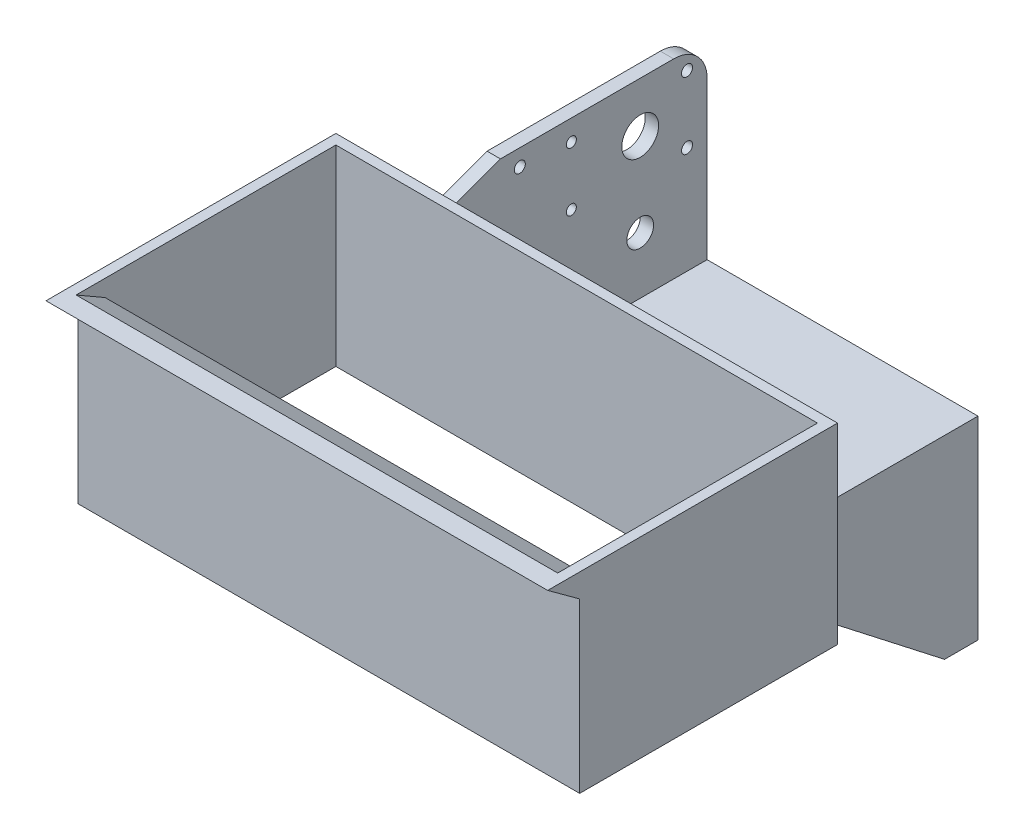
SolidWorks part; units mm, degrees
other "标注1"
sketch "草图12" plane through (40, 25, 80) normal (0.0849, 0.2202, 0.9717) x (0.9962, -0.0022, -0.0865)
ref_plane "前视基准面" through (0, 0, 0) normal (0, 0, 1) x (1, 0, 0)
ref_plane "上视基准面" through (0, 0, 0) normal (0, 1, 0) x (1, 0, 0)
ref_plane "右视基准面" through (0, 0, 0) normal (1, 0, 0) x (0, 0, -1)
sketch "草图1" plane through (0, 0, 0) normal (0, 0, 1) x (1, 0, 0)
  line L1 (-40, -25) -> (40, -25)
  line L2 (-40, -25) -> (-40, 25)
  line L3 (-40, 25) -> (40, 25)
  line L4 (40, -25) -> (40, 25)
  line L5 (-40, -25) -> (40, 25) construction
  line L6 (-40, 25) -> (40, -25) construction
  point P0 (0, 0)
  dimension "D1" = 80
  dimension "D2" = 50
extrude "凸台-拉伸1" add sketch "草图1" along normal blind 5
sketch "草图2" plane through (0, 0, 5) normal (0, 0, 1) x (1, 0, 0)
  line L0 (-1000, 0) -> (49000, 0) construction
  line L1 (0, -1000) -> (0, 49000) construction
  line L2 (-30, 20) -> (30, 20) construction
  line L3 (-30, 20) -> (-30, -20) construction
  line L4 (30, 20) -> (30, -20) construction
  line L5 (-30, -20) -> (30, -20) construction
  line L6 (0, 1000) -> (0, -49000) construction
  point P9 (0, 20)
  point P11 (30, 0)
  point P12 (-30, 0)
  point P14 (0, -20)
  dimension "D1" = 30
  dimension "D2" = 20
hole_wizard "M5 螺纹孔1" positions "草图3" profile "草图4" tap size "M5" standard "GB"
sketch "草图3" plane through (0, 0, 5) normal (0, 0, 1) x (1, 0, 0)
  point P0 (-30, 20)
  point P3 (-30, -20)
  point P6 (30, -20)
  point P9 (30, 20)
sketch "草图4" plane through (-30, 20, 5) normal (1, 0, 0) x (0, -1, 0)
  line L0 (0, 0) -> (0, 12.4)
  line L1 (0, 12.4) -> (2.1, 11.1382)
  line L2 (2.1, 11.1382) -> (2.1, 0)
  line L5 (2.1, 0) -> (0, 0)
  line L10 (0, 12.4) -> (-2.1, 11.1382) construction
  line L11 (0, -6.35) -> (0, 107.95) construction
  dimension "螺纹孔钻头直径" = 4.2
  dimension "螺纹孔钻头深度" = 12.4
  dimension "导头角度" = 118
cosmetic thread "孔螺蚊线1" parameters "D1"=10, "D2"=5
cosmetic thread "孔螺蚊线2" parameters "D1"=10, "D2"=5
cosmetic thread "孔螺蚊线3" parameters "D1"=10, "D2"=5
cosmetic thread "孔螺蚊线4" parameters "D1"=10, "D2"=5
sketch "草图5" plane through (40, 0, 0) normal (1, 0, 0) x (0, 0, -1)
  line L1 (0, -25) -> (-80, -25)
  line L2 (0, -25) -> (0, 25)
  line L3 (0, 25) -> (-80, 25)
  line L4 (-80, -25) -> (-80, 25)
  dimension "D1" = 50
  dimension "D2" = 80
extrude "凸台-拉伸2" add sketch "草图5" against normal blind 2 from offset 12 offset against normal yes
sketch "草图6" plane through (26, 0, 0) normal (-1, 0, 0) x (0, 0, 1)
  line L0 (11, 20) -> (61, 20) construction
  line L1 (61, 20) -> (61, 0) construction
  line L2 (61, 0) -> (11, 0) construction
  line L3 (11, 0) -> (11, 20) construction
  line L4 (5, 20) -> (5, -20) construction
  line L5 (5, 25) -> (80, 25) construction
  dimension "D1" = 50
  dimension "D2" = 20
  dimension "D3" = 6
  dimension "D4" = 5
hole_wizard "M4 螺纹孔1" positions "草图7" profile "草图8" tap size "M4" standard "GB"
sketch "草图7" plane through (26, 0, 0) normal (-1, 0, 0) x (0, 0, 1)
  point P0 (11, 20)
  point P3 (11, 0)
  point P6 (61, 20)
  point P9 (61, 0)
sketch "草图8" plane through (26, 20, 11) normal (0, 1, 0) x (0, 0, 1)
  line L0 (0, 0) -> (0, 10.1)
  line L1 (0, 10.1) -> (1.65, 9.1086)
  line L2 (1.65, 9.1086) -> (1.65, 0)
  line L5 (1.65, 0) -> (0, 0)
  line L10 (0, 10.1) -> (-1.65, 9.1086) construction
  line L11 (0, -6.35) -> (0, 107.95) construction
  dimension "螺纹孔钻头直径" = 3.3
  dimension "螺纹孔钻头深度" = 10.1
  dimension "导头角度" = 118
cosmetic thread "孔螺蚊线7" parameters "D1"=8, "D2"=4
cosmetic thread "孔螺蚊线8" parameters "D1"=8, "D2"=4
cosmetic thread "孔螺蚊线9" parameters "D1"=8, "D2"=4
cosmetic thread "孔螺蚊线10" parameters "D1"=8, "D2"=4
sketch "草图11" plane through (26, 0, 0) normal (-1, 0, 0) x (0, 0, 1)
  line L0 (25, 10) -> (62.4996, 10) construction
  line L2 (11, 0) -> (11, 20) construction
  line L5 (5, 25) -> (80, 25) construction
  line L9 (5, 25) -> (5, -25) construction
  circle A0 centre (25, 10) radius 5.5
  circle A1 centre (45.6, 18.75) radius 1.5
  circle A2 centre (45.6, 1.25) radius 1.5
  dimension "D1" = 11
  dimension "D2" = 3
  dimension "D3" = 17.5
  dimension "D4" = 20.6
  dimension "D5" = 15
  dimension "D6" = 20
extrude "切除-拉伸1" cut sketch "草图11" against normal through all
mirror "镜向1" about plane through (0, 0, 0) normal (1, 0, 0) of "凸台-拉伸2"
mirror "镜向2" about plane through (0, 0, 0) normal (1, 0, 0) of "M4 螺纹孔1", "切除-拉伸1"
cosmetic thread "孔螺蚊线11" parameters "D1"=8, "D2"=4
cosmetic thread "孔螺蚊线12" parameters "D1"=8, "D2"=4
cosmetic thread "孔螺蚊线13" parameters "D1"=8, "D2"=4
cosmetic thread "孔螺蚊线14" parameters "D1"=8, "D2"=4
sketch "草图13" plane through (0, -25, 0) normal (0, -1, 0) x (1, 0, 0)
  line L1 (-28, 80) -> (28, 80)
  line L2 (-28, 80) -> (-28, 5)
  line L3 (-28, 5) -> (28, 5)
  line L4 (28, 80) -> (28, 5)
  line L5 (-40, 5) -> (41.8748, 5)
  line L6 (-40, 5) -> (-40, -4.9337)
  line L7 (-40, -4.9337) -> (41.8748, -4.9337)
  line L8 (41.8748, 5) -> (41.8748, -4.9337)
  line M1 (-40, 0) -> (40, 0)
  line M2 (40, 0) -> (40, 5)
  line M3 (40, 5) -> (28, 5)
  line M4 (28, 5) -> (28, 80)
  line M5 (28, 80) -> (26, 80)
  line M6 (26, 80) -> (26, 5)
  line M7 (26, 5) -> (-26, 5)
  line M8 (-26, 5) -> (-26, 80)
  line M9 (-26, 80) -> (-28, 80)
  line M10 (-28, 80) -> (-28, 5)
  line M11 (-28, 5) -> (-40, 5)
  line M12 (-40, 5) -> (-40, 0)
extrude "切除-拉伸2" cut sketch "草图13" against normal through all both and the other way through all contours L3 M11 M12 M1 M2 M3 M7 | L8 L5 L6 L7 M2 M1 region at (0, -25, 2.5) region at (1.8445, -25, -2.3542)
sketch "草图14" plane through (0, 0, 5) normal (0, 0, -1) x (-1, 0, 0)
  line L1 (-28, 25) -> (28, 25)
  line L2 (-28, 25) -> (-28, -25)
  line L3 (-28, -25) -> (28, -25)
  line L4 (28, 25) -> (28, -25)
extrude "凸台-拉伸4" add sketch "草图13<3>" along normal blind 75 contours L1 M8 M7 M6 | L3 M10 M8 M9 | L3 M6 M4 M5 region at (-27, -25, 42.5) region at (0, -25, 42.5) region at (27, -25, 42.5)
sketch "草图13<3>" plane through (0, -25, 0) normal (0, -1, 0) x (1, 0, 0) same geometry as "草图13"
sketch "草图16" plane through (0, 0, 5) normal (0, 0, -1) x (-1, 0, 0)
  line L0 (0, -100) -> (0, -90.6573) construction
  line L2 (-28, -100) -> (28, -100) construction
  line L3 (-40, -100) -> (40, -100)
  line L4 (-40, -100) -> (-40, -46)
  line L5 (-40, -46) -> (40, -46)
  line L6 (40, -100) -> (40, -46)
  line L7 (12, -73) -> (0.1128, -73) construction
  circle A0 centre (-12, -83) radius 2.1
  circle A1 centre (12, -83) radius 2.1
  circle A2 centre (-12, -63) radius 2.1
  circle A3 centre (12, -63) radius 2.1
  point P15 (0, -46)
  dimension "D1" = 4.2
  dimension "D3" = 4.2
  dimension "D2" = 12
  dimension "D4" = 20
  dimension "D5" = 40
  dimension "D6" = 27
  dimension "D7" = 10
  dimension "D8" = 27
  dimension "D9" = 24
extrude "凸台-拉伸5" add sketch "草图16" against normal blind 10
sketch "草图17" plane through (0, 0, 80) normal (0, 0, 1) x (1, 0, 0)
  line L0 (-26, -49) -> (-26, -100)
  line L1 (26, -49) -> (26, -100)
  line L2 (-26, -49) -> (26, -49)
  line L3 (0, -100) -> (0, -92.4239) construction
  line L8 (28, -100) -> (28, 25)
  line L9 (28, 25) -> (26, 25)
  line L10 (26, 25) -> (26, -25)
  line L11 (26, -25) -> (-26, -25)
  line L12 (-26, -25) -> (-26, 25)
  line L13 (-26, 25) -> (-28, 25)
  line L14 (-28, 25) -> (-28, -100)
  line L15 (-28, -100) -> (28, -100)
  line L23 (-26, -100) -> (26, -100)
  dimension "D2" = 51
  dimension "D3" = 52
  dimension "D4" = 26
  dimension "D1" = 0
extrude "切除-拉伸4" cut sketch "草图17" against normal up to surface (65 mm away) up to face at (34, -73, 15)
sketch "草图18" plane through (0, 0, 80) normal (0, 0, 1) x (1, 0, 0)
  line L0 (0, -10.6953) -> (0, -25) construction
  line L1 (-50, 25) -> (50, 25)
  line L2 (-50, 25) -> (-50, -25)
  line L3 (-50, -25) -> (50, -25)
  line L4 (50, 25) -> (50, -25)
  line L5 (-26, -49) -> (26, -49) construction
  line L6 (-48, 25) -> (-48, -20)
  line L7 (48, 25) -> (48, -20)
  line L9 (-48, -20) -> (48, -20)
  point P5 (0, 25)
  line M11 (28, -100) -> (28, 25)
  line M13 (26, 25) -> (26, -25)
  line M14 (26, -25) -> (-26, -25)
  line M15 (-26, -25) -> (-26, 25)
  line M17 (-28, 25) -> (-28, -100)
  dimension "D1" = 50
  dimension "D2" = 50
  dimension "D3" = 74
  dimension "D4" = 2
  dimension "D5" = 2
  dimension "D6" = 5
extrude "凸台-拉伸6" add sketch "草图18" against normal up to surface (75 mm away) contours L9 L6 L1 L2 L3 M17 | L0 L9 L3 M15 | L9 L3 M17 M15 | L9 L0 M14 M13 | L9 L3 M13 M11 | L9 L3 L4 L1 L7 M11 region at (13, -22.5, 80) region at (-13, -22.5, 80) region at (-27, -22.5, 80) region at (27, -22.5, 80) region at (-28.5463, -22.5, 80) region at (38, -20.5463, 80)
sketch "草图19" plane through (-50, 0, 0) normal (-1, 0, 0) x (0, 0, 1)
  line L4 (80, 25) -> (5, 25)
  line L5 (5, 25) -> (5, -25)
  line L6 (5, -25) -> (80, -25)
  line L7 (80, -25) -> (80, 25)
  line L8 (80, 25) -> (5, 25)
  line L9 (5, 25) -> (5, -25)
  line L10 (5, -25) -> (80, -25)
  line L11 (80, -25) -> (80, 25)
  circle A0 centre (45.6, 1.25) radius 1.5 construction
  circle A1 centre (45.6, 18.75) radius 1.5 construction
  circle A2 centre (25, 10) radius 5.5 construction
  circle A3 centre (45.6, 1.25) radius 1.5
  circle A4 centre (45.6, 18.75) radius 1.5
  circle A5 centre (25, 10) radius 5.5
  dimension "D1" = 0
extrude "切除-拉伸5" cut sketch "草图19" against normal through all both and the other way through all contours A5 | A4 | A3 region at (-50, 1.25, 45.6) region at (-50, 18.75, 45.6) region at (-50, 10, 25)
sketch "草图20" plane through (-50, 0, 0) normal (-1, 0, 0) x (0, 0, 1)
  line L0 (61, 20) -> (61, 0) construction
  line L1 (61, 0) -> (11, 0) construction
  line L2 (11, 0) -> (11, 20) construction
  line L3 (11, 20) -> (61, 20) construction
  line L4 (61, 20) -> (61, 0) construction
  line L5 (61, 0) -> (11, 0) construction
  line L6 (11, 0) -> (11, 20) construction
  line L7 (11, 20) -> (61, 20) construction
ref_plane "基准面1" through (-50, 0, 0) normal (-1, 0, 0) x (0, 0, 1)
ref_plane "基准面2" through (-11, 0, 0) normal (-1, 0, 0) x (0, 0, 1)
mirror "镜向3" about plane through (-11, 0, 0) normal (-1, 0, 0) of "M4 螺纹孔1"
cosmetic thread "孔螺蚊线15" parameters "D1"=8, "D2"=4
cosmetic thread "孔螺蚊线16" parameters "D1"=8, "D2"=4
cosmetic thread "孔螺蚊线17" parameters "D1"=8, "D2"=4
cosmetic thread "孔螺蚊线18" parameters "D1"=8, "D2"=4
ref_plane "基准面3" through (50, 0, 0) normal (1, 0, 0) x (0, 0, -1)
ref_plane "基准面4" through (38, 0, 0) normal (1, 0, 0) x (0, 0, -1)
mirror "镜向4" about plane through (38, 0, 0) normal (1, 0, 0) of "M4 螺纹孔1"
cosmetic thread "孔螺蚊线19" parameters "D1"=8, "D2"=4
cosmetic thread "孔螺蚊线20" parameters "D1"=8, "D2"=4
cosmetic thread "孔螺蚊线21" parameters "D1"=8, "D2"=4
cosmetic thread "孔螺蚊线22" parameters "D1"=8, "D2"=4
sketch "草图21" plane through (0, 0, 80) normal (0, 0, 1) x (1, 0, 0)
  line L0 (-31.7586, 26.7655) -> (-31.7586, -20)
  line L1 (-48, -20) -> (-28, -20) construction
  line L2 (-31.7586, -20) -> (32.4376, -20)
  line L3 (28, -20) -> (48, -20) construction
  line L4 (32.4376, -20) -> (32.4376, 28.4059)
  line L5 (32.4376, 28.4059) -> (-31.7586, 26.7655)
extrude "切除-拉伸6" cut sketch "草图21" against normal through all both and the other way through all
sketch "草图22" plane through (0, 0, 80) normal (0, 0, 1) x (1, 0, 0)
  line L0 (-50, -25) -> (-28, -25) construction
  line L1 (-55, 25) -> (55, 25)
  line L2 (-55, 25) -> (-55, -25)
  line L3 (-55, -25) -> (55, -25)
  line L4 (55, 25) -> (55, -25)
  line L5 (-50, 25) -> (-48, 25) construction
  line L6 (0, -20) -> (0, 1.8911) construction
  line L8 (-53, 25) -> (-53, -20)
  line L9 (53, 25) -> (53, -20)
  line L10 (-53, -20) -> (53, -20)
  point P9 (0, 25)
  line M9 (48, -20) -> (-48, -20)
  line M12 (-50, 25) -> (-50, -25)
  line M13 (-50, -25) -> (-28, -25)
  line M21 (28, -25) -> (50, -25)
  line M22 (50, -25) -> (50, 25)
  dimension "D1" = 55
  dimension "D2" = 2
  dimension "D3" = 2
extrude "凸台-拉伸7" add sketch "草图22" against normal up to surface (75 mm away) contours L3 L6 L10 M12 M13 | L10 L8 L1 L2 L3 M12 | L6 L3 L10 M21 M22 M9 | L10 L3 L4 L1 L9 M22 region at (-53.6739, -2.9348, 80) region at (0, -22.5, 80) region at (53.6739, -2.9348, 80)
ref_plane "基准面6" through (-51.5, 0, 0) normal (1, 0, 0) x (0, 0, -1)
mirror "镜向8" about plane through (-51.5, 0, 0) normal (1, 0, 0) of "切除-拉伸5"
sketch "草图23" plane through (-55, 0, 0) normal (-1, 0, 0) x (0, 0, 1)
  line L0 (61, 20) -> (61, 0) construction
  line L1 (11, 20) -> (61, 20) construction
  line L2 (11, 0) -> (11, 20) construction
  line L3 (61, 0) -> (11, 0) construction
  line L4 (61, 20) -> (61, 0) construction
  line L5 (11, 20) -> (61, 20) construction
  line L6 (11, 0) -> (11, 20) construction
  line L7 (61, 0) -> (11, 0) construction
ref_plane "基准面7" through (2.5, 0, 0) normal (-1, 0, 0) x (0, 0, 1)
mirror "镜向16" about plane through (2.5, 0, 0) normal (-1, 0, 0) of "镜向3"
cosmetic thread "孔螺蚊线23" parameters "D1"=8, "D2"=4
cosmetic thread "孔螺蚊线24" parameters "D1"=8, "D2"=4
cosmetic thread "孔螺蚊线25" parameters "D1"=8, "D2"=4
cosmetic thread "孔螺蚊线26" parameters "D1"=8, "D2"=4
mirror "镜向18" about plane through (0, 0, 0) normal (1, 0, 0) of "镜向16"
cosmetic thread "孔螺蚊线27" parameters "D1"=8, "D2"=4
cosmetic thread "孔螺蚊线28" parameters "D1"=8, "D2"=4
cosmetic thread "孔螺蚊线29" parameters "D1"=8, "D2"=4
cosmetic thread "孔螺蚊线30" parameters "D1"=8, "D2"=4
sketch "草图24" plane through (0, 0, 5) normal (0, 0, -1) x (-1, 0, 0)
  line L0 (50, -20) -> (53, -20) construction
  line L1 (-51.4758, 28.456) -> (51.5, 28.456)
  line L2 (-51.4758, 28.456) -> (-51.4758, -20)
  line L3 (-51.4758, -20) -> (51.5, -20)
  line L4 (51.5, 28.456) -> (51.5, -20)
extrude "切除-拉伸7" cut sketch "草图24" against normal through all both and the other way through all
sketch "草图25" plane through (0, 0, 5) normal (0, 0, -1) x (-1, 0, 0)
  line L0 (0, -20) -> (0, -32.9926) construction
  line L6 (-55, 25) -> (-55, -25) construction
  line L7 (-53, -25) -> (-53, -32)
  line L8 (-53, -32) -> (53, -32)
  line L9 (-55, -25) -> (-55, -37)
  line L10 (-55, -37) -> (55, -37)
  line L11 (53, -25) -> (53, -32)
  line L12 (55, -25) -> (55, -37)
  line L13 (55, -25) -> (28, -25) construction
  line L14 (-55, -25) -> (-53, -25)
  line L15 (53, -25) -> (55, -25)
  point P13 (0, -37)
  point P16 (0, -32)
  dimension "D1" = 5
  dimension "D2" = 12
  dimension "D3" = 2
extrude "凸台-拉伸8" add sketch "草图25" against normal up to surface (75 mm away) up to face at (0, -33.625, 80)
sketch "草图26" plane through (0, 0, 5) normal (0, 0, -1) x (-1, 0, 0)
  line L0 (-53, -20) -> (-53, -32)
  line L1 (-53, -32) -> (53, -32)
  line L2 (53, -32) -> (53, -15.707)
  line L3 (53, 25) -> (53, -20) construction
  line L4 (53, -15.707) -> (-53, -15.707)
  line L5 (-53, 25) -> (-53, -20) construction
  line L6 (-53, -15.707) -> (-53, -20)
extrude "切除-拉伸8" cut sketch "草图26" against normal through all both and the other way through all
sketch "草图27" plane through (0, 0, 5) normal (0, 0, -1) x (-1, 0, 0)
  line L0 (0, -32) -> (0, -12.5887) construction
  line L2 (-59, 25) -> (-59, -37)
  line L3 (-59, -37) -> (59, -37)
  line L4 (59, 25) -> (59, -37)
  line L5 (55, 25) -> (55, -37) construction
  line L6 (-55, 25) -> (-55, -37) construction
  line L7 (-55, -37) -> (-28, -37) construction
  line L8 (59, 25) -> (57, 25)
  line L9 (57, 25) -> (57, -32)
  line L10 (57, -32) -> (-57, -32)
  line L11 (-57, -32) -> (-57, 25)
  line L12 (-57, 25) -> (-59, 25)
  line L13 (53, -32) -> (-53, -32) construction
  dimension "D1" = 4
  dimension "D2" = 4
  dimension "D3" = 2
  dimension "D4" = 2
  dimension "D5" = 62
extrude "凸台-拉伸9" add sketch "草图27" against normal up to surface (75 mm away) up to face at (0, -38.125, 80)
ref_plane "基准面8" through (56, 0, 0) normal (1, 0, 0) x (0, 0, -1)
mirror "镜向20" about plane through (56, 0, 0) normal (1, 0, 0) of "镜向8", "镜向16"
cosmetic thread "孔螺蚊线31" parameters "D1"=8, "D2"=4
cosmetic thread "孔螺蚊线32" parameters "D1"=8, "D2"=4
cosmetic thread "孔螺蚊线33" parameters "D1"=8, "D2"=4
cosmetic thread "孔螺蚊线34" parameters "D1"=8, "D2"=4
mirror "镜向22" about plane through (0, 0, 0) normal (1, 0, 0) of "镜向20"
cosmetic thread "孔螺蚊线35" parameters "D1"=8, "D2"=4
cosmetic thread "孔螺蚊线36" parameters "D1"=8, "D2"=4
cosmetic thread "孔螺蚊线37" parameters "D1"=8, "D2"=4
cosmetic thread "孔螺蚊线38" parameters "D1"=8, "D2"=4
sketch "草图28" plane through (0, 0, 5) normal (0, 0, -1) x (-1, 0, 0)
  line L0 (-56, 55) -> (-56, -55) construction
  line L1 (-56, 27.6586) -> (56, 27.6586)
  line L2 (-56, 27.6586) -> (-56, -32)
  line L3 (-56, -32) -> (56, -32)
  line L4 (56, 27.6586) -> (56, -32)
  line L5 (57, -32) -> (55, -32) construction
extrude "切除-拉伸9" cut sketch "草图28" against normal blind 100
sketch "草图29" plane through (0, 0, 80) normal (0, 0, 1) x (1, 0, 0)
  line L0 (0, -32) -> (0, -19.2163) construction
  line L2 (-75, 25) -> (75, 25)
  line L3 (28, 25) -> (-28, 25) construction
  line L4 (-75, 25) -> (-75, -37.1567)
  line L5 (-75, -37.1567) -> (75, -37.1567)
  line L6 (75, 25) -> (75, -37.1567)
  point P12 (0, 25)
  point P13 (0, -37.1567)
  dimension "D1" = 75
  dimension "D2" = 62.1567
extrude "凸台-拉伸10" add sketch "草图29" along normal blind 95
sketch "草图30" plane through (-75, 0, 0) normal (-1, 0, 0) x (0, 0, 1)
  line L0 (175, 25) -> (145, 7.6795)
  line L1 (145, 7.6795) -> (145, -37.1567)
  line L2 (175, -37.1567) -> (80, -37.1567) construction
  line L3 (175, 25) -> (175, -37.1567) construction
  dimension "D1" = 30
  dimension "D2" = 60
extrude "切除-拉伸10" cut sketch "草图30" against normal through all and the other way through all
sketch "草图31" plane through (-75, 0, 0) normal (-1, 0, 0) x (0, 0, 1)
  line L0 (83, 29.8275) -> (177.3615, 29.8275)
  line L1 (177.3615, 29.8275) -> (142, 9.4115)
  line L2 (142, 9.4115) -> (142, -50.3087)
  line L3 (142, -50.3087) -> (83, -50.3087)
  line L4 (83, -50.3087) -> (83, 29.8275)
  line L6 (80, 25) -> (80, -37.1567) construction
  line L7 (175, 25) -> (145, 7.6795) construction
  line L8 (145, 7.6795) -> (145, -37.1567) construction
  dimension "D2" = 3
  dimension "D3" = 3
  dimension "D4" = 3
extrude "切除-拉伸11" cut sketch "草图31" against normal offset from surface (144 mm away) 3 from offset 3 up to face at (75, -3.3268, 125) offset against normal yes
sketch "草图32" plane through (28, 0, 0) normal (1, 0, 0) x (0, 0, -1)
  line L0 (-80, -37.1567) -> (-15, -100)
  line L1 (-15, -100) -> (-94.5487, -113.2548)
  line L2 (-94.5487, -113.2548) -> (-80, -37.1567)
extrude "切除-拉伸12" cut sketch "草图32" along normal through all both and the other way through all
sketch "草图34" plane through (59, 0, 0) normal (1, 0, 0) x (0, 0, -1)
  line L0 (-80, 25) -> (-80, -37) construction
  line L1 (-5, 25) -> (-5, -25) construction
  line L3 (-14, -1.05) -> (-59, -1.05)
  line L4 (-80, 25) -> (-5, 25) construction
  line L5 (-59, -1.05) -> (-59, -4.05)
  line L6 (-59, -4.05) -> (-14, -4.05)
  line L7 (-14, -4.05) -> (-14, -1.05)
  dimension "D1" = 3
  dimension "D2" = 21
  dimension "D3" = 26.05
  dimension "D4" = 9
extrude "凸台-拉伸11" add sketch "草图34" along normal blind 20
extrude "凸台-拉伸12" add sketch "草图34<3>" against normal blind 20 from surface starting at face at (-59, 0, 59.35)
sketch "草图34<3>" plane through (59, 0, 0) normal (1, 0, 0) x (0, 0, -1) same geometry as "草图34"
sketch "草图35" plane through (0, 0, 5) normal (0, 0, -1) x (-1, 0, 0)
  line L0 (-28, -46) -> (-28, -100)
  line L5 (28, -46) -> (28, -100)
  line L10 (-40, -100) -> (40, -100)
  line L11 (40, -100) -> (40, -46)
  line L12 (40, -46) -> (-40, -46)
  line L13 (-40, -46) -> (-40, -100)
  line L14 (-40, -100) -> (40, -100)
  line L15 (40, -100) -> (40, -46)
  line L16 (40, -46) -> (-40, -46)
  line L17 (-40, -46) -> (-40, -100)
  circle A1 centre (12, -63) radius 2.1
  circle A2 centre (12, -63) radius 2.1
  circle A3 centre (-12, -63) radius 2.1
  circle A4 centre (-12, -63) radius 2.1
  circle A5 centre (12, -83) radius 2.1
  circle A6 centre (12, -83) radius 2.1
  circle A7 centre (-12, -83) radius 2.1
  circle A8 centre (-12, -83) radius 2.1
  point P0 (0, -71.1595)
  line M7 (-28, -46) -> (-40, -46)
  line M8 (-40, -46) -> (-40, -100)
  line M9 (-40, -100) -> (40, -100)
  line M10 (40, -100) -> (40, -46)
  line M11 (40, -46) -> (28, -46)
  dimension "D1" = 0
  dimension "D2" = 0
  dimension "D3" = 0
  dimension "D4" = 0
  dimension "D5" = 0
extrude "切除-拉伸13" cut sketch "草图35" against normal blind 10 contours A4 | A8 | A2 | A6 | L0 M7 M8 M9 | L5 M11 M9 M10 region at (34, -73, 5) region at (-34, -73, 5) region at (-12, -63, 5) region at (12, -63, 5) region at (-12, -83, 5) region at (12, -83, 5)
ref_plane "基准面9" through (-35, 0, 0) normal (1, 0, 0) x (0, 0, -1)
sketch "草图37" plane through (-35, 0, 0) normal (1, 0, 0) x (0, 0, -1)
  line L4 (-80, -37) -> (-5, -37)
  line L5 (-80, 25) -> (-80, -37)
  line L6 (-5, 25) -> (-80, 25)
  line L7 (-5, -37) -> (-5, 25)
  line L8 (-80, -37) -> (-5, -37)
  line L9 (-80, 25) -> (-80, -37)
  line L10 (-5, 25) -> (-80, 25)
  line L11 (-5, -37) -> (-5, 25)
  circle A0 centre (-11, 20) radius 1.65 construction
  circle A1 centre (-11, 0) radius 1.65 construction
  circle A2 centre (-45.6, 1.25) radius 1.5 construction
  circle A3 centre (-45.6, 18.75) radius 1.5 construction
  circle A4 centre (-25, 10) radius 5.5 construction
  circle A5 centre (-25, 10) radius 5.5
  circle A6 centre (-45.6, 18.75) radius 1.5
  circle A7 centre (-45.6, 1.25) radius 1.5
  circle A8 centre (-11, 0) radius 1.65
  circle A9 centre (-11, 20) radius 1.65
  circle A10 centre (-61, 20) radius 1.65 construction
  circle A11 centre (-61, 20) radius 1.65
  dimension "D1" = 0
extrude "凸台-拉伸13" add sketch "草图37" against normal blind 3
sketch "草图38" plane through (-38, 0, 0) normal (-1, 0, 0) x (0, 0, 1)
  line L4 (59, -1.05) -> (14, -1.05)
  line L5 (14, -1.05) -> (14, -4.05)
  line L6 (14, -4.05) -> (59, -4.05)
  line L7 (59, -4.05) -> (59, -1.05)
  line L8 (59, -1.05) -> (14, -1.05)
  line L9 (14, -1.05) -> (14, -4.05)
  line L10 (14, -4.05) -> (59, -4.05)
  line L11 (59, -4.05) -> (59, -1.05)
  dimension "D1" = 0
extrude "凸台-拉伸14" add sketch "草图38" along normal blind 20
sketch "草图39" plane through (0, 0, 80) normal (0, 0, -1) x (-1, 0, 0)
  line L0 (-42, -48.9981) -> (-42, 26.7782)
  line L2 (-42, 26.7782) -> (-75.2607, 26.7782)
  line L3 (-75.2607, 26.7782) -> (-96.9111, 26.7782)
  line L4 (-96.9111, 26.7782) -> (-96.9111, -48.9981)
  line L5 (-96.9111, -48.9981) -> (-42, -48.9981)
  line L6 (54.7, 26.7782) -> (54.7, -26.8557)
  line L7 (54.7, -26.8557) -> (38, -26.8557)
  line L8 (38, 25) -> (38, -32) construction
  line L9 (38, -26.8557) -> (38, -47.85)
  line L10 (38, -47.85) -> (95.8685, -47.85)
  line L11 (95.8685, -47.85) -> (95.8685, 12.0166)
  line L12 (95.8685, 12.0166) -> (66.1813, 27.9264)
  line L13 (66.1813, 27.9264) -> (54.7, 26.7782)
  line L15 (28, -100) -> (28, -37) construction
  dimension "D1" = 70
extrude "切除-拉伸17" cut sketch "草图39" along normal up to next contours L12 L13 L6 L7 L9 L10 L11 | L4 L5 L0 L2 L3 region at (-71.3932, -15.3982, 80)
sketch "草图40" plane through (-38, 0, 0) normal (-1, 0, 0) x (0, 0, 1)
  line L0 (5, -37) -> (5, 25) construction
  line L1 (5, 25) -> (80, 25) construction
  line L2 (42.5, 25) -> (42.5, -12.8603) construction
  circle A0 centre (25, -15) radius 4
  circle A1 centre (60, -15) radius 4
  dimension "D1" = 8
  dimension "D2" = 20
  dimension "D3" = 40
extrude "切除-拉伸18" cut sketch "草图40" against normal through all both and the other way through all
sketch "草图46" plane through (0, 0, 5) normal (0, 0, -1) x (-1, 0, 0)
  line L0 (12, -43.8944) -> (12, -95.6953) construction
  line L1 (28, -100) -> (28, -37) construction
  line L2 (-12, -83) -> (18.0205, -83) construction
  line L3 (-12, -63) -> (18.0205, -63) construction
  line L4 (-12, -63) -> (-43.3439, -63) construction
  line L5 (-12, -83) -> (-43.3439, -83) construction
  line L6 (4, -44.5419) -> (4, -84.5112) construction
  line L7 (-20, -41.7847) -> (-20, -84.5112) construction
  line L8 (-28, -43.8944) -> (-28, -90) construction
  line L10 (-28, -100) -> (28, -100) construction
  line L11 (-28, -90) -> (14.1348, -90) construction
  circle A0 centre (4, -63) radius 2.1
  circle A1 centre (-20, -63) radius 2.1
  circle A2 centre (-20, -83) radius 2.1
  circle A3 centre (4, -83) radius 2.1
  dimension "D3" = 4.2
  dimension "D5" = 4.2
  dimension "D7" = 4.2
  dimension "D8" = 4.2
  dimension "D1" = 16
  dimension "D2" = 8
  dimension "D4" = 24
  dimension "D6" = 8
  dimension "D9" = 10
sketch "草图48" plane through (0, 0, 5) normal (0, 0, -1) x (-1, 0, 0)
  line L1 (-15.9536, -56.9415) -> (-8.4612, -56.9415)
  line L2 (-15.9536, -56.9415) -> (-15.9536, -86.6527)
  line L3 (-15.9536, -86.6527) -> (-8.4612, -86.6527)
  line L4 (-8.4612, -56.9415) -> (-8.4612, -86.6527)
  line L5 (8.5904, -56.9415) -> (17.2454, -56.9415)
  line L6 (8.5904, -56.9415) -> (8.5904, -86.6527)
  line L7 (8.5904, -86.6527) -> (17.2454, -86.6527)
  line L8 (17.2454, -56.9415) -> (17.2454, -86.6527)
extrude "凸台-拉伸18" add sketch "草图48" against normal up to surface (10 mm away) up to face at (9.9, -83, 15)
sketch "草图49" plane through (0, 0, 5) normal (0, 0, -1) x (-1, 0, 0)
  line L0 (-28, -90) -> (12, -90)
  line L1 (12, -43.8944) -> (12, -95.6953) construction
  line L2 (-28, -90) -> (14.1348, -90) construction
  line L3 (12, -90) -> (12, -37.1567)
  line L4 (12, -37.1567) -> (28, -37)
  line L5 (28, -37) -> (28, -104.6086)
  line L6 (28, -104.6086) -> (-42.5646, -106.288)
  line L7 (-42.5646, -106.288) -> (-39.8518, -88.332)
  line L8 (-39.8518, -88.332) -> (-28, -90)
extrude "切除-拉伸20" cut sketch "草图49" against normal through all both and the other way through all
sketch "草图50" plane through (26, 0, 0) normal (-1, 0, 0) x (0, 0, 1)
  line L4 (15, -49) -> (15, -90)
  line L5 (15, -90) -> (25.3432, -90)
  line L6 (25.3432, -90) -> (67.7502, -49)
  line L7 (67.7502, -49) -> (15, -49)
  line L8 (15, -49) -> (15, -90)
  line L9 (15, -90) -> (25.3432, -90)
  line L10 (25.3432, -90) -> (67.7502, -49)
  line L11 (67.7502, -49) -> (15, -49)
  dimension "D1" = 0
sketch "草图51" plane through (0, 0, 5) normal (0, 0, -1) x (-1, 0, 0)
  circle A0 centre (4, -63) radius 2.1 construction
  circle A1 centre (4, -83) radius 2.1 construction
  circle A2 centre (-20, -83) radius 2.1 construction
  circle A3 centre (-20, -63) radius 2.1 construction
  circle A4 centre (4, -63) radius 2.1
  circle A5 centre (4, -83) radius 2.1
  circle A6 centre (-20, -83) radius 2.1
  circle A7 centre (-20, -63) radius 2.1
extrude "切除-拉伸22" cut sketch "草图50" against normal blind 2
sketch "草图52" plane through (0, 0, 5) normal (0, 0, -1) x (-1, 0, 0)
  line L1 (-45, -37) -> (-45, -90)
  line L2 (-42, -37) -> (-28, -37) construction
  line L3 (-45, -90) -> (-28, -90)
  line L5 (-28, -37) -> (-45, -37)
  line L6 (-17, -63) -> (13.0205, -63) construction
  line L7 (-17, -83) -> (13.0205, -83) construction
  line L8 (-17, -83) -> (-48.3439, -83) construction
  line L9 (-8, -44.5419) -> (-8, -84.5112) construction
  line L10 (-32, -41.7847) -> (-32, -84.5112) construction
  line L11 (-17, -63) -> (-48.3439, -63) construction
  line L12 (-28, -90) -> (14.1348, -90) construction
  line L13 (12, -43.8944) -> (12, -95.6953) construction
  line L14 (-28, -90) -> (-28, -37) construction
  line L15 (-28, -37) -> (-28, -90)
  line L16 (-12, -83) -> (18.0205, -83) construction
  line L17 (-12, -63) -> (18.0205, -63) construction
  line L19 (-12, -83) -> (-43.3439, -83) construction
  circle A4 centre (-8, -63) radius 2.1
  circle A5 centre (-8, -83) radius 2.1
  circle A6 centre (-32, -83) radius 2.1
  circle A7 centre (-32, -63.1479) radius 2.1
  dimension "D3" = 4.2
  dimension "D4" = 4.2
  dimension "D5" = 4.2
  dimension "D6" = 4.2
  dimension "D10" = 20
  dimension "D1" = 20
  dimension "D2" = 27
  dimension "D7" = 24
  dimension "D11" = 13
sketch "草图53" plane through (28, 0, 0) normal (1, 0, 0) x (0, 0, -1)
  line L7 (-67.7502, -49) -> (-15, -49)
  line L8 (-15, -49) -> (-15, -90)
  line L9 (-15, -90) -> (-5, -90)
  line L10 (-5, -90) -> (-5, -37)
  line L11 (-5, -37) -> (-80, -37)
  line L12 (-80, -37) -> (-80, -37.1567)
  line L13 (-80, -37.1567) -> (-67.7502, -49)
  line L14 (-67.7502, -49) -> (-15, -49)
  line L15 (-15, -49) -> (-15, -90)
  line L16 (-15, -90) -> (-5, -90)
  line L17 (-5, -90) -> (-5, -37)
  line L18 (-5, -37) -> (-80, -37)
  line L19 (-80, -37) -> (-80, -37.1567)
  line L20 (-80, -37.1567) -> (-67.7502, -49)
  dimension "D1" = 0
extrude "凸台-拉伸20" add sketch "草图53" along normal up to surface (14 mm away) up to face at (42, -34.5, 42.5)
extrude "切除-拉伸23" cut sketch "草图52" against normal through all both and the other way through all contours A7 | A6 | A4 | A5
sketch "草图55" plane through (0, -32, 0) normal (0, 1, 0) x (1, 0, 0)
  line L0 (5.2591, -30.6339) -> (5.2591, -90.5479) construction
  line L1 (-35, -80) -> (42, -80) construction
  line L2 (-19.4818, -35) -> (-7.4818, -35)
  line L3 (-19.4818, -35) -> (-19.4818, -60)
  line L4 (-19.4818, -60) -> (-7.4818, -60)
  line L5 (-7.4818, -35) -> (-7.4818, -60)
  line L6 (18, -35) -> (30, -35)
  line L7 (18, -35) -> (18, -60)
  line L8 (18, -60) -> (30, -60)
  line L9 (30, -35) -> (30, -60)
  line L10 (42, -5) -> (42, -80) construction
  dimension "D1" = 12
  dimension "D2" = 20
  dimension "D3" = 20
  dimension "D4" = 25
  dimension "D5" = 25
  dimension "D6" = 12
extrude "切除-拉伸24" cut sketch "草图55" against normal through all both and the other way through all
sketch "草图56" plane through (42, 0, 0) normal (1, 0, 0) x (0, 0, -1)
  line L0 (-15, -90) -> (-67.7502, -49)
  line L1 (-67.7502, -49) -> (-15, -49)
  line L2 (-15, -49) -> (-15, -90)
extrude "凸台-拉伸21" add sketch "草图56" against normal blind 3
sketch "草图58" plane through (39, 0, 0) normal (-1, 0, 0) x (0, 0, 1)
  line L3 (15, -49) -> (15, -90)
  line L4 (15, -90) -> (67.7502, -49)
  line L5 (67.7502, -49) -> (15, -49)
  line L6 (15, -49) -> (15, -90)
  line L7 (15, -90) -> (67.7502, -49)
  line L8 (67.7502, -49) -> (15, -49)
  dimension "D1" = 0
extrude "凸台-拉伸22" add sketch "草图58" against normal blind 3 from surface starting at face at (-12, -58.7189, 18.3333)
sketch "草图59" plane through (75, 0, 0) normal (1, 0, 0) x (0, 0, -1)
  line L0 (-80, 5) -> (-95.3438, -37.1567)
  line L1 (-80, 25) -> (-80, -32) construction
  line L2 (-145, -37.1567) -> (-80, -37.1567) construction
  line L4 (-95.3438, -37.1567) -> (-80, -37.1567)
  line L5 (-80, -37.1567) -> (-80, 5)
  dimension "D1" = 70
  dimension "D2" = 20
extrude "凸台-拉伸23" add sketch "草图59" against normal up to surface (147 mm away) up to face at (-72, -2.9804, 123.8)
sketch "草图60" plane through (0, -90, 0) normal (0, -1, 0) x (1, 0, 0)
  line L0 (12, 5) -> (43.3439, 5) construction
  line L1 (-9, 15) -> (39, 15)
  line L2 (-9, 15) -> (-9, 10)
  line L3 (-9, 10) -> (39, 10)
  line L4 (39, 15) -> (39, 10)
  line L5 (42, 15) -> (42, 5) construction
  dimension "D1" = 5
  dimension "D2" = 3
extrude "切除-拉伸26" cut sketch "草图60" against normal up to surface (41 mm away) contours L1 L4 L3 L2 up to face at (24, -49, 47.5)
sketch "草图61" plane through (0, -37.1567, 0) normal (0, -1, 0) x (1, 0, 0)
  line L0 (42, 80) -> (75, 80) construction
  line L1 (-72, 95.3438) -> (72, 95.3438)
  line L2 (-72, 95.3438) -> (-72, 85)
  line L3 (-72, 85) -> (72, 85)
  line L4 (72, 95.3438) -> (72, 85)
  dimension "D1" = 5
  dimension "D2" = 144
extrude "切除-拉伸27" cut sketch "草图61" against normal blind 167
sketch "草图62" plane through (75, 0, 0) normal (1, 0, 0) x (0, 0, -1)
  line L0 (-145, -37.1567) -> (-154.5518, -37.1567)
  line L1 (-154.5518, -37.1567) -> (-154.5518, 13.1942)
  line L2 (-145, 7.6795) -> (-175, 25) construction
  line L3 (-145, -37.1567) -> (-145, 7.6795) construction
  line L9 (-145, -37.1567) -> (-80, -37.1567)
  line L10 (-80, -37.1567) -> (-80, 25)
  line L11 (-80, 25) -> (-175, 25)
  line L12 (-175, 25) -> (-145, 7.6795)
  line L13 (-145, 7.6795) -> (-145, -37.1567)
  line L17 (-154.5518, 13.1942) -> (-145, 7.6795)
  line L18 (-145, 7.6795) -> (-145, -37.1567)
  dimension "D1" = 9.5518
  dimension "D2" = 0
extrude "凸台-拉伸24" add sketch "草图62" against normal up to surface (150 mm away) up to face at (-75, -3.3268, 125)
sketch "草图64" plane through (0, 0, 0) normal (0, 1, 0) x (1, 0, 0)
  line L1 (-72, -142) -> (72, -142)
  line L5 (72, -142) -> (72, -152)
  line L6 (72, -169) -> (72, -142) construction
  line L7 (72, -152) -> (-72, -152)
  line L8 (-72, -169) -> (-72, -83) construction
  line L9 (-72, -152) -> (-72, -142)
  dimension "D1" = 10
  dimension "D2" = 144
extrude "切除-拉伸28" cut sketch "草图64" against normal blind 167 and the other way blind 167
sketch "草图65" plane through (0, 0, 154.5518) normal (0, 0, 1) x (1, 0, 0)
  line L4 (-75, 13.1942) -> (-75, -37.1567)
  line L5 (-75, -37.1567) -> (75, -37.1567)
  line L6 (75, -37.1567) -> (75, 13.1942)
  line L7 (75, 13.1942) -> (-75, 13.1942)
  line L8 (-75, 13.1942) -> (-75, -37.1567)
  line L9 (-75, -37.1567) -> (75, -37.1567)
  line L10 (75, -37.1567) -> (75, 13.1942)
  line L11 (75, 13.1942) -> (-75, 13.1942)
  dimension "D1" = 0
extrude "凸台-拉伸25" add sketch "草图65" along normal blind 2.55 separate body
sketch "草图66" plane through (-75, 0, 0) normal (-1, 0, 0) x (0, 0, 1)
  line L0 (80, 25) -> (80, 21)
  line L1 (80, 25) -> (80, -37) construction
  line L2 (80, 21) -> (168.0718, 21)
  line L3 (175, 25) -> (154.5518, 13.1942) construction
  line L4 (168.0718, 21) -> (175, 25)
  line L5 (175, 25) -> (80, 25)
  dimension "D1" = 4
extrude "切除-拉伸29" cut sketch "草图66" against normal blind 215.55
sketch "草图67" plane through (-75, 0, 0) normal (-1, 0, 0) x (0, 0, 1)
  line L0 (157.1018, 13.1942) -> (166.6762, 20.1942)
  line L1 (168.0718, 21) -> (154.5518, 13.1942) construction
  line L2 (166.6762, 20.1942) -> (154.5518, 13.1942)
  line L3 (154.5518, -37.1567) -> (154.5518, 13.1942) construction
  line L4 (157.1018, 13.1942) -> (154.5518, 13.1942) construction
  line L5 (154.5518, 13.1942) -> (157.1018, 13.1942)
  dimension "D1" = 7
extrude "凸台-拉伸26" add sketch "草图67" against normal up to surface (150 mm away) up to face at (75, -3.8238, 127.4351)
sketch "草图68" plane through (-75, 0, 0) normal (-1, 0, 0) x (0, 0, 1)
  line L0 (80, 21) -> (80, 20.1942)
  line L1 (80, 21) -> (80, -37) construction
  line L2 (80, 20.1942) -> (166.6762, 20.1942)
  line L3 (157.1018, 13.1942) -> (166.6762, 20.1942)
  line L4 (166.6762, 20.1942) -> (154.5518, 13.1942)
  line L5 (154.5518, 13.1942) -> (157.1018, 13.1942)
  line L6 (157.1018, 13.1942) -> (166.6762, 20.1942)
  line L7 (166.6762, 20.1942) -> (154.5518, 13.1942)
  line L8 (154.5518, 13.1942) -> (157.1018, 13.1942)
  line L9 (168.0718, 21) -> (80, 21)
  line L10 (166.6762, 20.1942) -> (168.0718, 21)
  line M4 (80, 21) -> (80, -37.1567)
  line M8 (166.6762, 20.1942) -> (168.0718, 21)
  line M9 (168.0718, 21) -> (80, 21)
  dimension "D1" = 0
extrude "切除-拉伸30" cut sketch "草图68" against normal blind 215.55 contours L2 M4 M8 M9 region at (-75, 20.5982, 123.6879)
sketch "草图69" plane through (-38, 0, 0) normal (-1, 0, 0) x (0, 0, 1)
  line L0 (80, 20.1942) -> (66.7963, 25)
  line L1 (5, 25) -> (80, 25) construction
  line L2 (66.7963, 25) -> (80, 25)
  line L3 (80, 25) -> (80, 20.1942)
  dimension "D1" = 20
extrude "切除-拉伸31" cut sketch "草图69" against normal blind 215.55
sketch "草图70" plane through (0, 20.1942, 0) normal (0, 1, 0) x (1, 0, 0)
  line L0 (72, -83) -> (72, -160.6762) construction
  line L1 (-72, -83) -> (72, -83)
  line L2 (-72, -83) -> (-72, -87.9738)
  line L3 (-72, -87.9738) -> (72, -87.9738)
  line L4 (72, -83) -> (72, -87.9738)
extrude "切除-拉伸32" cut sketch "草图70" against normal through all both and the other way through all
fillet "圆角1" radius 10 1 edges at (-36.5, 25, 5)
sketch "草图71" plane through (-35, 0, 0) normal (1, 0, 0) x (0, 0, -1)
  line L5 (-5, -32) -> (-5, 15)
  line L6 (-15, 25) -> (-66.7963, 25)
  line L7 (-66.7963, 25) -> (-80, 20.1942)
  line L8 (-80, 20.1942) -> (-80, -32)
  line L9 (-80, -32) -> (-5, -32)
  line L10 (-5, -32) -> (-5, 15)
  line L11 (-15, 25) -> (-66.7963, 25)
  line L12 (-66.7963, 25) -> (-80, 20.1942)
  line L13 (-80, 20.1942) -> (-80, -32)
  line L14 (-80, -32) -> (-5, -32)
  circle A0 centre (-25, -15) radius 4 construction
  arc A1 (-5, 15) -> (-15, 25) centre (-15, 15) ccw
  arc A2 (-5, 15) -> (-15, 25) centre (-15, 15) ccw
  circle A3 centre (-11, 0) radius 1.65 construction
  circle A4 centre (-11, 20) radius 1.65 construction
  circle A5 centre (-25, 10) radius 5.5 construction
  circle A6 centre (-45.6, 18.75) radius 1.5 construction
  circle A7 centre (-45.6, 1.25) radius 1.5 construction
  circle A8 centre (-60, -15) radius 4 construction
  circle A9 centre (-61, 20) radius 1.65 construction
  circle A10 centre (-25, -15) radius 4
  circle A11 centre (-11, 0) radius 1.65
  circle A12 centre (-11, 20) radius 1.65
  circle A13 centre (-25, 10) radius 5.5
  circle A14 centre (-45.6, 18.75) radius 1.5
  circle A15 centre (-45.6, 1.25) radius 1.5
  circle A16 centre (-60, -15) radius 4
  circle A17 centre (-61, 20) radius 1.65
  dimension "D1" = 0
sketch "草图72" plane through (0, 0, 14) normal (0, 0, -1) x (-1, 0, 0)
  line L4 (54.7, -4.05) -> (54.7, -1.05)
  line L5 (54.7, -1.05) -> (38, -1.05)
  line L6 (38, -1.05) -> (38, -4.05)
  line L7 (38, -4.05) -> (54.7, -4.05)
  line L8 (54.7, -4.05) -> (54.7, -1.05)
  line L9 (54.7, -1.05) -> (38, -1.05)
  line L10 (38, -1.05) -> (38, -4.05)
  line L11 (38, -4.05) -> (54.7, -4.05)
  dimension "D1" = 0
extrude "切除-拉伸33" cut sketch "草图72" against normal blind 54.5
extrude "凸台-拉伸27" add sketch "草图71" against normal blind 8
sketch "草图73" plane through (0, 0, 80) normal (0, 0, -1) x (-1, 0, 0)
  line L1 (43, -32) -> (38, -32)
  line L2 (43, -32) -> (43, -37)
  line L3 (43, -37) -> (38, -37)
  line L4 (38, -32) -> (38, -37)
extrude "凸台-拉伸28" add sketch "草图73" along normal up to surface (75 mm away)
sketch "草图74" plane through (0, 0, 5) normal (0, 0, -1) x (-1, 0, 0)
  line L0 (43, -37) -> (43, 15) construction
  line L1 (35, 25) -> (39, 25)
  line L2 (35, 25) -> (35, -32)
  line L3 (35, -32) -> (39, -32)
  line L4 (39, 25) -> (39, -32)
  dimension "D1" = 4
extrude "切除-拉伸34" cut sketch "草图74" against normal up to surface (75 mm away) up to face at (27.3333, -16.3208, 80)
